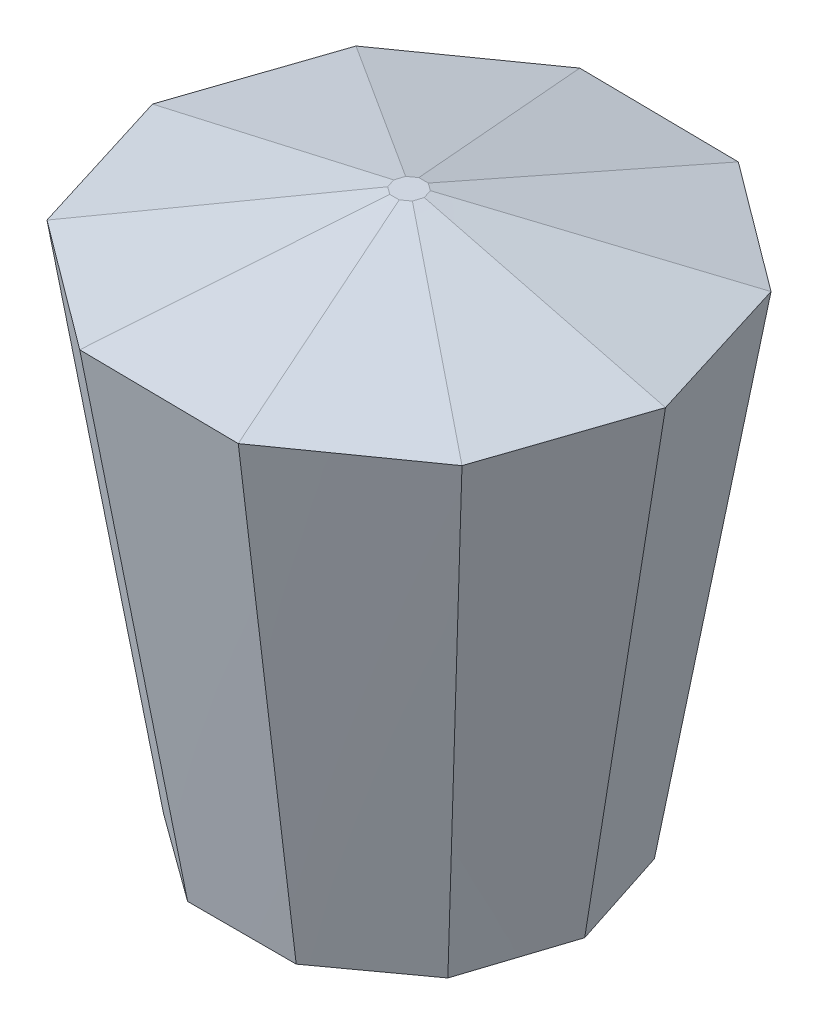
SolidWorks part; units mm, degrees
material "CA"
ref_plane "Front Plane" through (0, 0, 0) normal (0, 0, 1) x (1, 0, 0)
ref_plane "Top Plane" through (0, 0, 0) normal (0, 1, 0) x (1, 0, 0)
ref_plane "Right Plane" through (0, 0, 0) normal (1, 0, 0) x (0, 0, -1)
sketch "Croquis1" plane through (0, 0, 0) normal (0, 1, 0) x (1, 0, 0)
  line L1 (-6.0459, 0) -> (-4.8912, -3.5537)
  line L2 (-4.8912, -3.5537) -> (-1.8683, -5.75)
  line L3 (-1.8683, -5.75) -> (1.8683, -5.75)
  line L4 (1.8683, -5.75) -> (4.8912, -3.5537)
  line L5 (4.8912, -3.5537) -> (6.0459, 0)
  line L6 (6.0459, 0) -> (4.8912, 3.5537)
  line L7 (4.8912, 3.5537) -> (1.8683, 5.75)
  line L8 (1.8683, 5.75) -> (-1.8683, 5.75)
  line L9 (-1.8683, 5.75) -> (-4.8912, 3.5537)
  line L10 (-4.8912, 3.5537) -> (-6.0459, 0)
  circle A0 centre (0, 0) radius 5.75 construction
  dimension "D1" = 11.5
ref_plane "Plano1" through (0, 17.3, 0) normal (0, 1, 0) x (1, 0, 0)
sketch "Croquis2" plane through (0, 17.3, 0) normal (0, 1, 0) x (1, 0, 0)
  line L1 (-8.9368, 0.1099) -> (-7.2946, -5.164)
  line L2 (-7.2946, -5.164) -> (-2.8661, -8.4654)
  line L3 (-2.8661, -8.4654) -> (2.6571, -8.5333)
  line L4 (2.6571, -8.5333) -> (7.1654, -5.3418)
  line L5 (7.1654, -5.3418) -> (8.9368, -0.1099)
  line L6 (8.9368, -0.1099) -> (7.2946, 5.164)
  line L7 (7.2946, 5.164) -> (2.8661, 8.4654)
  line L8 (2.8661, 8.4654) -> (-2.6571, 8.5333)
  line L9 (-2.6571, 8.5333) -> (-7.1654, 5.3418)
  line L10 (-7.1654, 5.3418) -> (-8.9368, 0.1099)
  circle A0 centre (0, 0) radius 8.5 construction
  dimension "D1" = 17
loft "Recubrir1" add profiles "Croquis1", "Croquis2" connector at (1.8683, 0, 5.75) connector at (2.6571, 17.3, 8.5333)
ref_plane "Plano2" through (0, 19.3, 0) normal (0, 1, 0) x (1, 0, 0)
sketch "Croquis4" plane through (0, 19.3, 0) normal (0, 1, 0) x (1, 0, 0)
  line L1 (-0.5257, 0) -> (-0.4253, -0.309)
  line L2 (-0.4253, -0.309) -> (-0.1625, -0.5)
  line L3 (-0.1625, -0.5) -> (0.1625, -0.5)
  line L4 (0.1625, -0.5) -> (0.4253, -0.309)
  line L5 (0.4253, -0.309) -> (0.5257, 0)
  line L6 (0.5257, 0) -> (0.4253, 0.309)
  line L7 (0.4253, 0.309) -> (0.1625, 0.5)
  line L8 (0.1625, 0.5) -> (-0.1625, 0.5)
  line L9 (-0.1625, 0.5) -> (-0.4253, 0.309)
  line L10 (-0.4253, 0.309) -> (-0.5257, 0)
  circle A0 centre (0, 0) radius 0.5 construction
  dimension "D1" = 1
loft "Recubrir2" add profiles "Croquis4", "Croquis2<3>" connector at (-0.5257, 19.3, 0) connector at (-8.9368, 17.3, -0.1099)
sketch "Croquis2<3>" plane through (0, 17.3, 0) normal (0, 1, 0) x (1, 0, 0) same geometry as "Croquis2"
sketch "Croquis5" plane through (0, 0, 0) normal (0, -1, 0) x (1, 0, 0)
  circle A0 centre (0, 0) radius 1.5
  dimension "D1" = 3
extrude "Cortar-Extruir1" cut sketch "Croquis5" against normal blind 19
